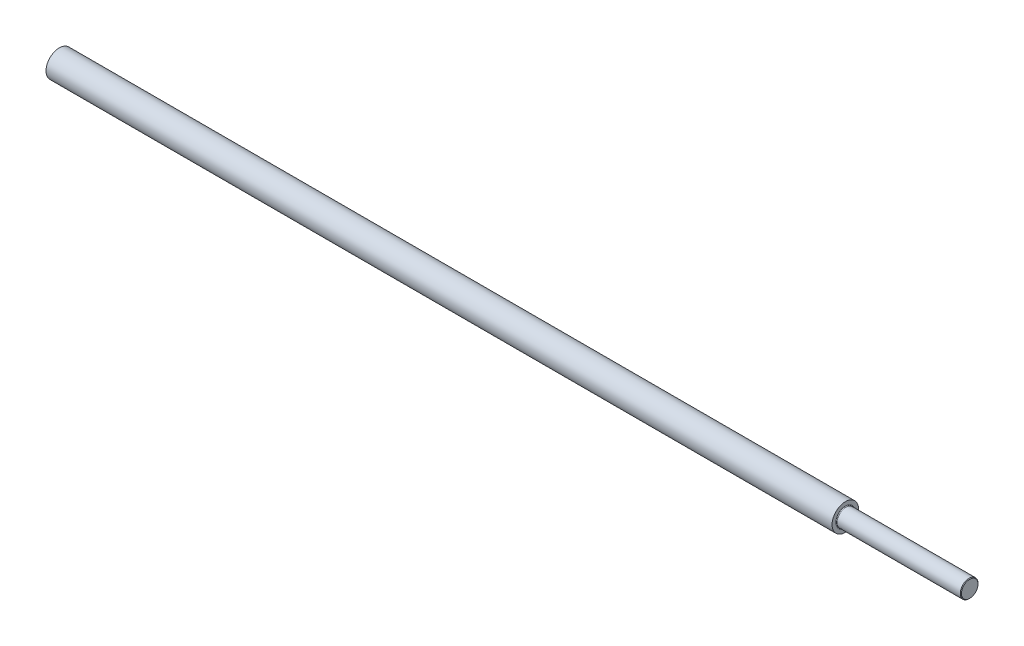
SolidWorks part; units mm, degrees
ref_plane "Front Plane" through (0, 0, 0) normal (0, 0, 1) x (1, 0, 0)
ref_plane "Top Plane" through (0, 0, 0) normal (0, 1, 0) x (1, 0, 0)
ref_plane "Right Plane" through (0, 0, 0) normal (1, 0, 0) x (0, 0, -1)
ref_plane "Plane1" through (0, 0, 0) normal (0, 0, 1) x (1, 0, 0)
sketch "Sketch1" plane through (0, 0, 0) normal (0, 0, 1) x (1, 0, 0)
  line L0 (0, 0) -> (0, 6)
  line L1 (0, 6) -> (354, 6)
  line L2 (354, 6) -> (354, 4.3)
  line L3 (354.3, 4) -> (409.7333, 4)
  line L4 (409.7333, 4) -> (410, 3.7333)
  line L5 (410, 3.7333) -> (410, 0)
  line L6 (410, 0) -> (0, 0)
  line L7 (410, 0) -> (0, 0) construction
  arc A0 (354, 4.3) -> (354.3, 4) centre (354.3, 4.3) ccw
  dimension "D7" = 0.3
  dimension "D1" = 410
  dimension "D2" = 56
  dimension "D3" = 6
  dimension "D4" = 4
  dimension "D5" = 0.2667
  dimension "D6" = 135
revolve "Revolve1" add sketch "Sketch1" angle 360 about L7 reverse direction yes
cosmetic thread "Cosmetic Thread1" parameters "D1"=370, "D2"=9.5
